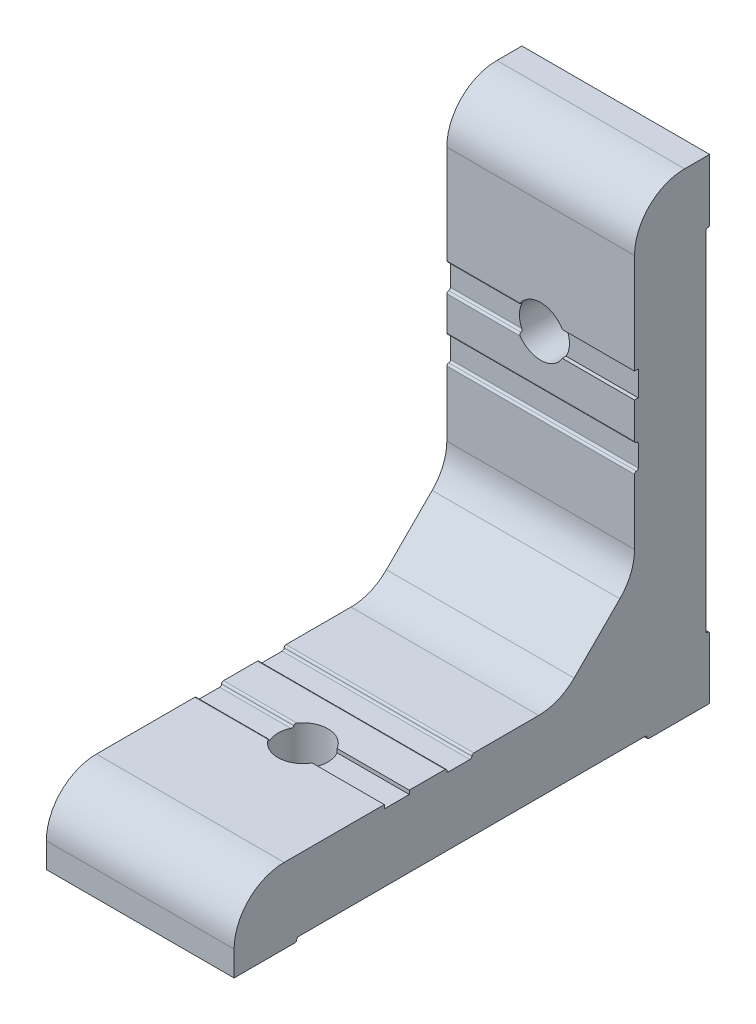
SolidWorks part; units mm, degrees
ref_plane "Plano frontal" through (0, 0, 0) normal (0, 0, 1) x (1, 0, 0)
ref_plane "Plano superior" through (0, 0, 0) normal (0, 1, 0) x (1, 0, 0)
ref_plane "Plano direito" through (0, 0, 0) normal (1, 0, 0) x (0, 0, -1)
ref_plane "Plano1" through (10, 0, 0) normal (1, 0, 0) x (0, 0, -1)
sketch "Esboço1" plane through (10, 0, 0) normal (1, 0, 0) x (0, 0, -1)
  line L0 (7, 38) -> (-31, 38)
  line L1 (-31, 38) -> (-31, 0)
  line L2 (-31, 0) -> (7, 0)
  line L3 (7, 0) -> (7, 38)
  dimension "D1" = 38
extrude "Ressalto-extrusão1" add sketch "Esboço1" against normal blind 15
sketch "Esboço2" plane through (-5, 0, 0) normal (-1, 0, 0) x (0, 0, 1)
  line L0 (31, 38) -> (-1, 38)
  line L1 (-1, 38) -> (-1, 12)
  line L2 (-1, 12) -> (5, 6)
  line L3 (5, 6) -> (31, 6)
  line L4 (31, 6) -> (31, 38)
  line L5 (31, 0) -> (-7, 0) construction
  line L6 (-7, 0) -> (-7, 38) construction
  line L7 (-7, 38) -> (31, 38) construction
  dimension "D1" = 6
  dimension "D2" = 6
  dimension "D3" = 6
  dimension "D4" = 6
extrude "Corte-extrusão1" cut sketch "Esboço2" against normal through all
sketch "Esboço7" plane through (10, 0, 0) normal (1, 0, 0) x (0, 0, -1)
  line L0 (7, 0) -> (7, 38) construction
  line L1 (7, 33) -> (6.7, 33)
  line L2 (7, 33) -> (7, 5)
  line L3 (7, 5) -> (6.7, 5)
  line L4 (6.7, 33) -> (6.7, 5)
  line L5 (-31, 0) -> (7, 0) construction
  line L6 (2, 0) -> (-26, 0)
  line L7 (2, 0) -> (2, 0.3)
  line L8 (2, 0.3) -> (-26, 0.3)
  line L9 (-26, 0) -> (-26, 0.3)
  line L10 (7, 38) -> (1, 38) construction
  line L11 (-31, 6) -> (-31, 0) construction
  line L12 (-5, 6) -> (-31, 6) construction
  line L13 (-14, 6) -> (-12, 6)
  line L14 (-14, 6) -> (-14, 5.7)
  line L15 (-14, 5.7) -> (-12, 5.7)
  line L16 (-12, 6) -> (-12, 5.7)
  line L17 (1, 38) -> (1, 12) construction
  line L18 (1, 21) -> (1.3, 21)
  line L19 (1, 21) -> (1, 19)
  line L20 (1, 19) -> (1.3, 19)
  line L21 (1.3, 21) -> (1.3, 19)
  line L22 (-19, 6) -> (-19, 5.7)
  line L23 (-17, 6) -> (-17, 5.7)
  line L24 (-19, 6) -> (-17, 6)
  line L25 (-19, 5.7) -> (-17, 5.7)
  line L26 (1.3, 26) -> (1.3, 24)
  line L27 (1, 26) -> (1, 24)
  line L28 (1, 26) -> (1.3, 26)
  line L29 (1, 24) -> (1.3, 24)
  point P28 (-13, 5.7)
  point P29 (1.3, 20)
  point P34 (-18, 5.7)
  point P39 (1.3, 25)
  dimension "D1" = 5
  dimension "D2" = 5
  dimension "D3" = 5
  dimension "D4" = 5
  dimension "D5" = 0.3
  dimension "D6" = 0.3
  dimension "D7" = 2
  dimension "D8" = 0.3
  dimension "D9" = 2
  dimension "D10" = 0.3
  dimension "D11" = 20
  dimension "D12" = 20
extrude "Corte-extrusão2" cut sketch "Esboço7" against normal through all
hole_wizard "Furo de diâmetro Ø7.0 (7)3" positions "Esboço4" profile "Esboço3" hole size "Ø7.0" standard "Ansi Metric" end condition through all
sketch "Esboço4" plane through (0, 6, 0) normal (0, 1, 0) x (1, 0, 0)
  line L0 (10, -31) -> (-5, -31) construction
  line L1 (-5, 7) -> (10, 7) construction
  point P0 (2.5, -18)
  point P3 (2.5, -31)
  dimension "D1" = 25
sketch "Esboço3" plane through (2.5, 6, 18) normal (1, 0, 0) x (0, 0, 1)
  line L0 (0, 0) -> (0, 6)
  line L1 (0, 6) -> (2, 6)
  line L2 (2, 6) -> (2, 0)
  line L5 (2, 0) -> (0, 0)
  line L11 (0, -6.35) -> (0, 107.95) construction
  dimension "Thru Hole Dia." = 4
  dimension "Thru Hole Depth" = 6
hole_wizard "Furo de diâmetro Ø7.0 (7)2" positions "Esboço6" profile "Esboço5" hole size "Ø7.0" standard "Ansi Metric" end condition through all
sketch "Esboço6" plane through (0, 0, -7) normal (0, 0, -1) x (-1, 0, 0)
  line L0 (5, 38) -> (-10, 38) construction
  line L1 (5, 0) -> (-10, 0) construction
  point P0 (-2.5, 25)
  point P3 (-2.5, 38)
  dimension "D1" = 25
sketch "Esboço5" plane through (2.5, 25, -7) normal (1, 0, 0) x (0, 1, 0)
  line L0 (0, 0) -> (0, 38)
  line L1 (0, 38) -> (2, 38)
  line L2 (2, 38) -> (2, 0)
  line L5 (2, 0) -> (0, 0)
  line L11 (0, -6.35) -> (0, 107.95) construction
  dimension "Thru Hole Dia." = 4
  dimension "Thru Hole Depth" = 38
fillet "Filete1" radius 4 4 edges at (2.5, 6, 31) (2.5, 6, 5) (2.5, 38, -1) (2.5, 12, -1)
fillet "Filete2" radius 0.15 24 edges at (2.5, 5, -7) (2.5, 5, -6.7) (2.5, 33, -7) (2.5, 33, -6.7) (2.5, 0, 26) (2.5, 0.3, 26) (2.5, 0.3, -2) (2.5, 0, -2) (2.5, 19, -1.3) (2.5, 19, -1) (2.5, 21, -1.3) (2.5, 21, -1) (2.5, 5.7, 14) (2.5, 6, 14) (2.5, 5.7, 12) (2.5, 6, 12) (-2.116, 26, -1.3) (-2.116, 24, -1.3) (-2.116, 24, -1) (-2.116, 26, -1) (-2.116, 5.7, 19) (-2.116, 5.7, 17) (-2.116, 6, 17) (-2.116, 6, 19)
ref_plane "Plano2" [suppressed] through (2.5, 0, 0) normal (-1, 0, 0) x (0, 0, 1)
equation "\"D2@Esboço2\"=\"D1@Esboço2\""
